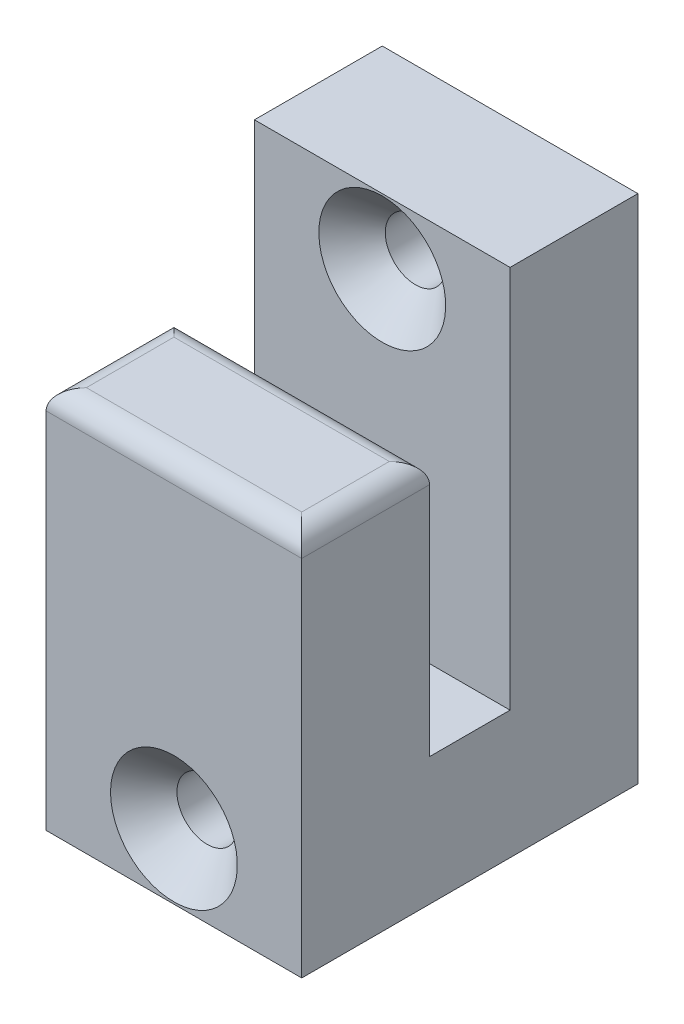
SolidWorks part; units mm, degrees
ref_plane "Front Plane" through (0, 0, 0) normal (0, 0, 1) x (1, 0, 0)
ref_plane "Top Plane" through (0, 0, 0) normal (0, 1, 0) x (1, 0, 0)
ref_plane "Right Plane" through (0, 0, 0) normal (1, 0, 0) x (0, 0, -1)
sketch "Sketch1" plane through (0, 0, 0) normal (1, 0, 0) x (0, 0, -1)
  line L0 (-1.6143, 16.3286) -> (-14.3143, 16.3286)
  line L1 (19.0857, -21.7714) -> (-14.3143, -21.7714)
  line L2 (19.0857, -21.7714) -> (19.0857, 29.0286)
  line L3 (19.0857, 29.0286) -> (6.3857, 29.0286)
  line L4 (-14.3143, -21.7714) -> (-14.3143, 16.3286)
  line L5 (19.0857, -21.7714) -> (-14.3143, 16.3286) construction
  line L6 (19.0857, 29.0286) -> (-14.3143, -21.7714) construction
  line L8 (6.3857, 29.0286) -> (6.3857, -9.0714)
  line L9 (6.3857, -9.0714) -> (-1.6143, -9.0714)
  line L10 (-1.6143, 16.3286) -> (-1.6143, -9.0714)
  line L11 (6.3857, -9.0714) -> (6.3857, -21.7714) construction
  point P0 (0, 0)
  point P10 (0, 0)
  dimension "D1" = 12.7
  dimension "D2" = 8
  dimension "D3" = 25.4
  dimension "D4" = 12.7
extrude "Boss-Extrude1" add sketch "Sketch1" along normal blind 25.4
sketch "Sketch2" plane through (0, 0, -19.0857) normal (0, 0, -1) x (-1, 0, 0)
  line L0 (-12.7, 29.0286) -> (-12.7, -21.7714) construction
  line L1 (-25.4, 29.0286) -> (0, 29.0286) construction
  line L2 (-25.4, -21.7714) -> (0, -21.7714) construction
  line L3 (-12.7, 22.5286) -> (-12.7, 29.0286) construction
  line L4 (-12.7, -15.2714) -> (-12.7, -21.7714) construction
  circle A0 centre (-12.7, 22.5286) radius 3
  circle A1 centre (-12.7, -15.2714) radius 3
  dimension "D1" = 6
  dimension "D2" = 6.5
extrude "Cut-Extrude1" cut sketch "Sketch2" against normal through all
chamfer "Chamfer1" distance 3.3 angle 45 2 edges at (9.7, -15.2714, 14.3143) (12.7, 25.5286, -6.3857)
fillet "Fillet1" radius 2 4 edges at (12.7, 16.3286, 1.6143) (25.4, 16.3286, 7.9643) (12.7, 16.3286, 14.3143) (0, 16.3286, 7.9643)
